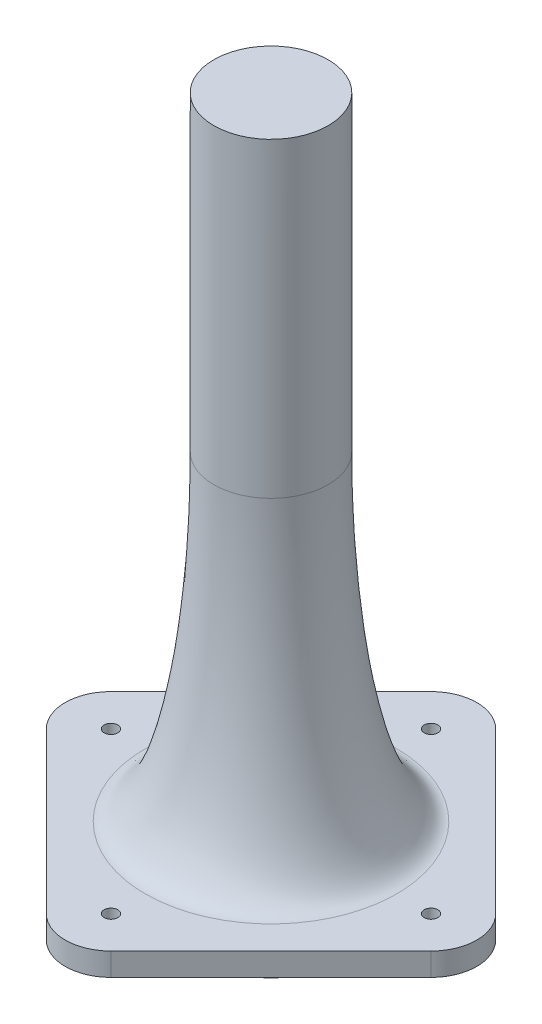
SolidWorks part; units mm, degrees
ref_plane "Alzado" through (0, 0, 0) normal (0, 0, 1) x (1, 0, 0)
ref_plane "Planta" through (0, 0, 0) normal (0, 1, 0) x (1, 0, 0)
ref_plane "Vista lateral" through (0, 0, 0) normal (1, 0, 0) x (0, 0, -1)
sketch "Croquis1" plane through (0, 0, 0) normal (0, 1, 0) x (1, 0, 0)
  circle A0 centre (0, 0) radius 12.5
  dimension "D1" = 25
extrude "Saliente-Extruir1" add sketch "Croquis1" along normal blind 150
sketch "Croquis2" plane through (0, 0, 0) normal (0, -1, 0) x (1, 0, 0)
  circle A0 centre (0, 0) radius 25
  dimension "D1" = 50
extrude "Saliente-Extruir2" add sketch "Croquis2" against normal blind 7
sketch "Croquis3" plane through (0, 7, 0) normal (0, 1, 0) x (1, 0, 0)
  line L0 (35, 0) -> (-35, 0) construction
  line L1 (0, 35) -> (0, -35) construction
  line L2 (-7.0711, 42.0711) -> (-42.0711, 7.0711)
  line L3 (7.0711, 42.0711) -> (42.0711, 7.0711)
  line L4 (-42.0711, -7.0711) -> (-7.0711, -42.0711)
  line L5 (42.0711, -7.0711) -> (7.0711, -42.0711)
  line L6 (0, 0) -> (45, 0) construction
  arc A0 (-42.0711, 7.0711) -> (-42.0711, -7.0711) centre (-35, 0) ccw
  arc A1 (7.0711, 42.0711) -> (-7.0711, 42.0711) centre (0, 35) ccw
  arc A2 (42.0711, -7.0711) -> (42.0711, 7.0711) centre (35, 0) ccw
  arc A3 (-7.0711, -42.0711) -> (7.0711, -42.0711) centre (0, -35) ccw
  circle A4 centre (-35, 0) radius 1.5
  circle A5 centre (0, 35) radius 1.5
  circle A6 centre (35, 0) radius 1.5
  circle A7 centre (0, -35) radius 1.5
  point P5 (0, 0)
  point P8 (0, 0)
  dimension "D3" = 20
  dimension "D4" = 3
  dimension "D1" = 70
extrude "Saliente-Extruir3" add sketch "Croquis3" along normal blind 5
fillet "Redondeo1" radius 15 1 edges at (0, 12, 12.5) second distance 70 first distance on face at (0, 12, 12.5)
